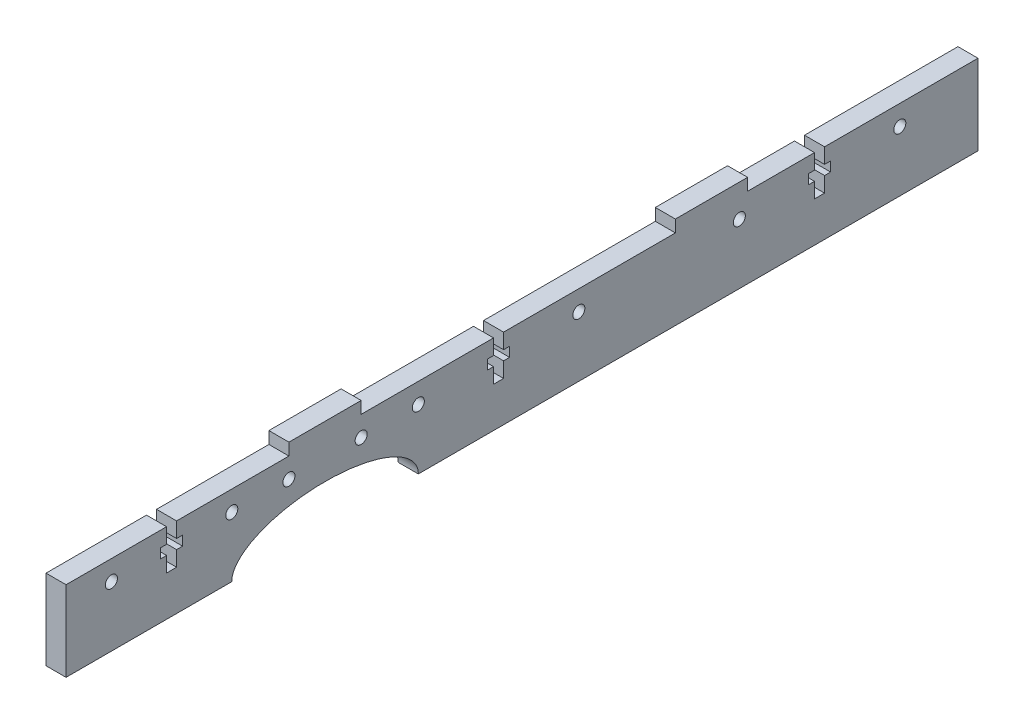
SolidWorks part; units mm, degrees
material "PMMA"
ref_plane "Front Plane" through (0, 0, 0) normal (0, 0, 1) x (1, 0, 0)
ref_plane "Top Plane" through (0, 0, 0) normal (0, 1, 0) x (1, 0, 0)
ref_plane "Right Plane" through (0, 0, 0) normal (1, 0, 0) x (0, 0, -1)
sketch "Schizzo1" plane through (0, 0, 0) normal (1, 0, 0) x (0, 0, -1)
  line L0 (-115.445, 5) -> (-2.745, 5) construction
  line L1 (-113.645, -10) -> (113.645, -10)
  line L2 (-113.645, -10) -> (-113.645, 10)
  line L3 (-113.645, 10) -> (-58.095, 10)
  line L4 (113.645, -10) -> (113.645, 10)
  line L5 (-49.095, 10) -> (-49.095, -10) construction
  line L6 (-58.095, 10) -> (-58.095, 13)
  line L7 (-58.095, 13) -> (-40.095, 13)
  line L8 (-40.095, 13) -> (-40.095, 10)
  line L9 (-40.095, 10) -> (113.645, 10)
  line L10 (-113.645, 10) -> (113.645, -10) construction
  point P8 (0, 0)
  dimension "D2" = 20
  dimension "D3" = 9
  dimension "D4" = 9
  dimension "D5" = 3
  dimension "D1" = 55.55
  dimension "D6" = 5
  dimension "D8" = 153.74
extrude "Estrusione-Estrusione1" add sketch "Schizzo1" along normal blind 5
sketch "Schizzo3" plane through (0, 0, 0) normal (1, 0, 0) x (0, 0, -1)
  line L1 (-40.095, 13) -> (-58.095, 13) construction
  line L2 (-113.645, -10) -> (113.645, -10) construction
  line L4 (-49.095, 13) -> (-49.095, -10) construction
  line L5 (-113.645, 5) -> (113.645, 5) construction
  line L10 (-58.095, 10) -> (-113.645, 10) construction
  line L11 (-113.645, 10) -> (-113.645, -10) construction
  line L12 (113.645, -10) -> (113.645, 10) construction
  circle A0 centre (-58.095, 5) radius 1.5
  circle A1 centre (-72.345, 5) radius 1.5
  circle A2 centre (-40.095, 5) radius 1.5
  circle A3 centre (-25.845, 5) radius 1.5
  circle A4 centre (14.155, 5) radius 1.5
  circle A5 centre (54.155, 5) radius 1.5
  circle A6 centre (94.155, 5) radius 1.5
  circle A7 centre (-102.345, 5) radius 1.5
  ellipse E0 centre (-49.095, -10) end of major axis (-25.845, -10) minor radius 10
  dimension "D3" = 3
  dimension "D6" = 3
  dimension "D4" = 4
  dimension "D1" = 9
  dimension "D2" = 23.25
  dimension "D5" = 2
  dimension "D8" = 5
extrude "Taglio-Estrusione1" cut sketch "Schizzo3" along direction (-1, 0, 0) on the side of the normal through all
sketch "Schizzo5" plane through (0, 0, 0) normal (1, 0, 0) x (0, 0, -1)
  line L0 (-100.845, 5) -> (-73.845, 5) construction
  line L1 (-24.345, 5) -> (12.655, 5) construction
  line L2 (55.655, 5) -> (92.655, 5) construction
  line L3 (-5.845, 0) -> (-5.845, 10) construction
  line L4 (-87.345, 0) -> (-87.345, 10) construction
  line L5 (-88.595, 0) -> (-88.595, 3.8)
  line L6 (-88.595, 3.8) -> (-90.095, 3.8)
  line L7 (-90.095, 3.8) -> (-90.095, 6.2)
  line L8 (-90.095, 6.2) -> (-88.595, 6.2)
  line L9 (-88.595, 6.2) -> (-88.595, 10)
  line L10 (-88.595, 10) -> (-86.095, 10)
  line L11 (-86.095, 10) -> (-86.095, 6.2)
  line L12 (-86.095, 6.2) -> (-84.595, 6.2)
  line L13 (-84.595, 6.2) -> (-84.595, 3.8)
  line L14 (-84.595, 3.8) -> (-86.095, 3.8)
  line L15 (-86.095, 3.8) -> (-86.095, 0)
  line L16 (-86.095, 0) -> (-88.595, 0)
  line L17 (-58.095, 10) -> (-113.645, 10) construction
  line L18 (-7.095, 0) -> (-7.095, 3.8)
  line L19 (-7.095, 3.8) -> (-8.595, 3.8)
  line L20 (-8.595, 3.8) -> (-8.595, 6.2)
  line L21 (-8.595, 6.2) -> (-7.095, 6.2)
  line L22 (-7.095, 6.2) -> (-7.095, 10)
  line L23 (-7.095, 10) -> (-4.595, 10)
  line L24 (-4.595, 10) -> (-4.595, 6.2)
  line L25 (-4.595, 6.2) -> (-3.095, 6.2)
  line L26 (-3.095, 6.2) -> (-3.095, 3.8)
  line L27 (-3.095, 3.8) -> (-4.595, 3.8)
  line L28 (-4.595, 3.8) -> (-4.595, 0)
  line L29 (-4.595, 0) -> (-7.095, 0)
  line L30 (113.645, 10) -> (-40.095, 10) construction
  line L31 (74.155, 0) -> (74.155, 10) construction
  line L32 (72.905, 0) -> (72.905, 3.8)
  line L33 (72.905, 3.8) -> (71.405, 3.8)
  line L34 (71.405, 3.8) -> (71.405, 6.2)
  line L35 (71.405, 6.2) -> (72.905, 6.2)
  line L36 (72.905, 6.2) -> (72.905, 10)
  line L37 (72.905, 10) -> (75.405, 10)
  line L38 (75.405, 10) -> (75.405, 6.2)
  line L39 (75.405, 6.2) -> (76.905, 6.2)
  line L40 (76.905, 6.2) -> (76.905, 3.8)
  line L41 (76.905, 3.8) -> (75.405, 3.8)
  line L42 (75.405, 3.8) -> (75.405, 0)
  line L43 (75.405, 0) -> (72.905, 0)
  line L44 (113.645, 10) -> (-40.095, 10) construction
  line L45 (-113.645, 10) -> (-113.645, -10) construction
  circle A0 centre (-102.345, 5) radius 1.5 construction
  circle A1 centre (-72.345, 5) radius 1.5 construction
  circle A2 centre (-25.845, 5) radius 1.5 construction
  circle A3 centre (14.155, 5) radius 1.5 construction
  circle A4 centre (54.155, 5) radius 1.5 construction
  circle A5 centre (94.155, 5) radius 1.5 construction
  point P39 (-87.345, 5)
  point P40 (-87.345, 0)
  point P53 (-5.845, 0)
  point P55 (-5.845, 5)
  point P72 (74.155, 0)
  point P73 (74.155, 5)
  dimension "D1" = 2.4
  dimension "D2" = 10
  dimension "D3" = 90
  dimension "D4" = 90
  dimension "D5" = 2.5
  dimension "D6" = 3.8
  dimension "D7" = 5.5
  dimension "D8" = 2.4
  dimension "D9" = 10
  dimension "D10" = 90
  dimension "D11" = 90
  dimension "D12" = 2.5
  dimension "D13" = 3.8
  dimension "D14" = 5.5
  dimension "D15" = 2.4
  dimension "D16" = 10
  dimension "D17" = 90
  dimension "D18" = 90
  dimension "D19" = 2.5
  dimension "D20" = 3.8
  dimension "D21" = 5.5
  dimension "D22" = 26.3
  dimension "D23" = 107.8
  dimension "D24" = 187.8
extrude "Taglio-Estrusione2" cut sketch "Schizzo5" along normal through all
sketch "Schizzo6" plane through (0, 10, 0) normal (0, 1, 0) x (1, 0, 0)
  line L0 (5, 72.905) -> (5, -4.595) construction
  line L1 (0, 56.225) -> (5, 56.225)
  line L2 (0, 56.225) -> (0, 38.225)
  line L3 (0, 38.225) -> (5, 38.225)
  line L4 (5, 56.225) -> (5, 38.225)
  line L5 (0, 72.905) -> (0, -4.595) construction
  line L6 (5, 113.645) -> (0, 113.645) construction
  point P8 (2.5, 113.645)
  dimension "D1" = 18
  dimension "D2" = 57.42
extrude "Estrusione-Estrusione2" add sketch "Schizzo6" along normal blind 3
equation "\"Thickness5\"=5"
equation "\"D1@Estrusione-Estrusione1\"=\"Thickness5\""
equation "\"D5@Schizzo1\"=\"Thickness3\""
equation "\"D1@Estrusione-Estrusione2\"=\"Thickness3\""
equation "\"Thickness3\"= 3"
